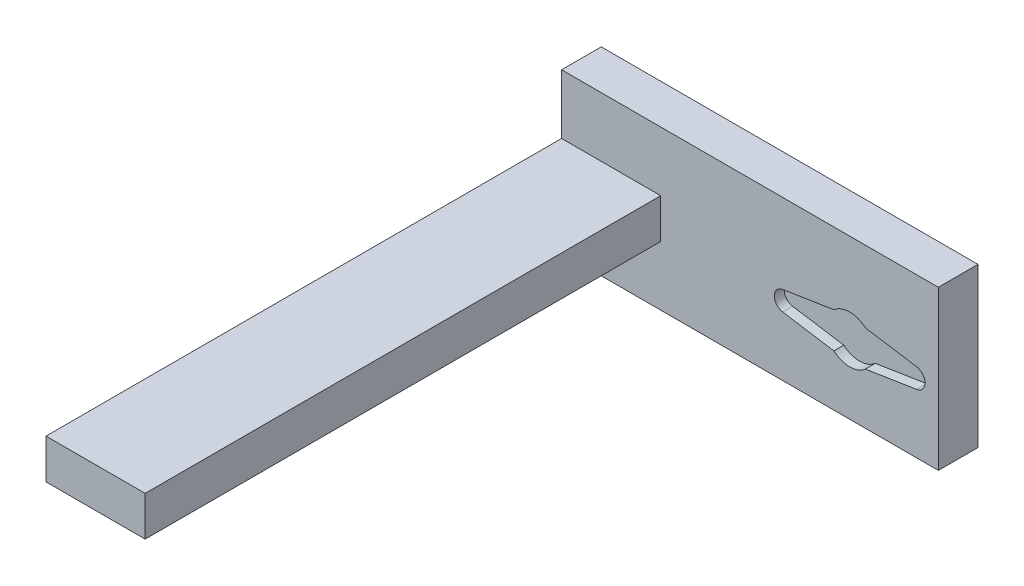
SolidWorks part; units mm, degrees
ref_plane "Front Plane" through (0, 0, 0) normal (0, 0, 1) x (1, 0, 0)
ref_plane "Top Plane" through (0, 0, 0) normal (0, 1, 0) x (1, 0, 0)
ref_plane "Right Plane" through (0, 0, 0) normal (1, 0, 0) x (0, 0, -1)
sketch "Sketch3" plane through (0, 0, 0) normal (0, 0, 1) x (1, 0, 0)
  line L1 (-22.6388, -7.4411) -> (22.3612, -7.4411)
  line L2 (-22.6388, -7.4411) -> (-22.6388, 7.5589)
  line L3 (-22.6388, 7.5589) -> (22.3612, 7.5589)
  line L4 (22.3612, -7.4411) -> (22.3612, 7.5589)
  dimension "D1" = 15
  dimension "D2" = 45
extrude "Boss-Extrude1" add sketch "Sketch3" against normal blind 10
sketch "Sketch2" plane through (0, 0, 0) normal (0, 0, 1) x (1, 0, 0)
  line L0 (-16.8881, 2.4697) -> (-3.9686, 4.5)
  line L1 (-16.8881, -2.4697) -> (-3.9686, -4.5)
  line L2 (3.9686, 4.5) -> (16.8881, 2.4697)
  line L3 (16.8881, -2.4697) -> (3.9686, -4.5)
  arc A0 (-16.8881, 2.4697) -> (-16.8881, -2.4697) centre (-16.5, 0) ccw
  arc A1 (-3.9686, 4.5) -> (3.9686, 4.5) centre (0, 0) cw
  arc A2 (-3.9686, -4.5) -> (3.9686, -4.5) centre (0, 0) ccw
  arc A3 (16.8881, -2.4697) -> (16.8881, 2.4697) centre (16.5, 0) ccw
extrude "Cut-Extrude1" cut sketch "Sketch2" against normal blind 2.5
sketch "Sketch11" plane through (0, -7.4411, 0) normal (0, -1, 0) x (1, 0, 0)
  line L0 (8.25, 0) -> (-8.25, 0) construction
  line L1 (22.3612, -10) -> (-22.6388, -10)
  line L2 (22.3612, -10) -> (22.3612, 0)
  line L3 (22.3612, 0) -> (-22.6388, 0)
  line L4 (-22.6388, -10) -> (-22.6388, 0)
  line L5 (-22.6388, -10) -> (-22.6388, 0) construction
extrude "Boss-Extrude5" add sketch "Sketch11" along normal blind 10
sketch "Sketch14" plane through (0, 7.5589, 0) normal (0, 1, 0) x (1, 0, 0)
  line L0 (-8.25, 0) -> (8.25, 0) construction
  line L1 (22.3612, 10) -> (-22.6388, 10)
  line L2 (22.3612, 10) -> (22.3612, 0)
  line L3 (22.3612, 0) -> (-22.6388, 0)
  line L4 (-22.6388, 10) -> (-22.6388, 0)
  line L5 (-22.6388, 10) -> (-22.6388, 0) construction
extrude "Boss-Extrude7" add sketch "Sketch14" along normal blind 15
sketch "Sketch20" plane through (-22.6388, 0, 0) normal (-1, 0, 0) x (0, 0, 1)
  line L0 (0, -22) -> (0, 22) construction
  line L1 (-10, 22.5589) -> (0, 22.5589)
  line L2 (-10, 22.5589) -> (-10, -17.4411)
  line L3 (-10, -17.4411) -> (0, -17.4411)
  line L4 (0, 22.5589) -> (0, -17.4411)
  line L5 (0, -17.4411) -> (-10, -17.4411) construction
extrude "Boss-Extrude10" add sketch "Sketch20" along normal blind 50
sketch "Sketch21" plane through (0, 0, 0) normal (0, 0, 1) x (1, 0, 0)
  line L0 (-72.6388, -17.4411) -> (-72.6388, 22.5589) construction
  line L1 (-72.6388, 7.5589) -> (-47.6388, 7.5589)
  line L2 (-72.6388, 7.5589) -> (-72.6388, -2.4411)
  line L3 (-72.6388, -2.4411) -> (-47.6388, -2.4411)
  line L4 (-47.6388, 7.5589) -> (-47.6388, -2.4411)
  line L5 (-72.6388, 22.5589) -> (22.3612, 22.5589) construction
  dimension "D1" = 25
  dimension "D2" = 10
  dimension "D3" = 15
extrude "Boss-Extrude11" add sketch "Sketch21" along normal blind 130
